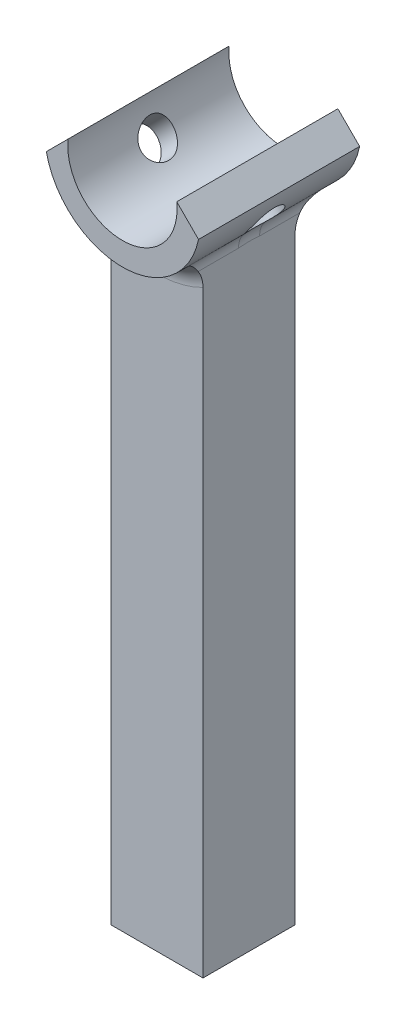
SolidWorks part; units mm, degrees
ref_plane "Front Plane" through (0, 0, 0) normal (0, 0, 1) x (1, 0, 0)
ref_plane "Top Plane" through (0, 0, 0) normal (0, 1, 0) x (1, 0, 0)
ref_plane "Right Plane" through (0, 0, 0) normal (1, 0, 0) x (0, 0, -1)
sketch "Sketch1" plane through (0, 0, 0) normal (0, 1, 0) x (1, 0, 0)
  line L1 (4, -15) -> (-4, -15)
  line L2 (4, -15) -> (4, -7)
  line L3 (4, -7) -> (-4, -7)
  line L4 (-4, -15) -> (-4, -7)
  point P4 (0, -7)
  dimension "D3" = 8
  dimension "D4" = 8
extrude "Boss-Extrude1" add sketch "Sketch1" against normal blind 55 contours L2 L3 L4 L1
sketch "Sketch2" plane through (0, 0, 0) normal (0, 0, 1) x (1, 0, 0)
  line L0 (-3.6183, 0) -> (3.4011, 0) construction
  line L1 (-8, 2) -> (8, 2) construction
  line L2 (-8, 2) -> (-4.4083, 5.5917)
  line L3 (8, 2) -> (3.6742, 6.3258)
  circle A0 centre (0, 4.75) radius 4.75
  circle A1 centre (0, 4.75) radius 6.75
  point P2 (-0.1086, 0)
  dimension "D1" = 0
  dimension "D3" = 2
  dimension "D4" = 45
  dimension "D5" = 45
  dimension "D6" = 8
  dimension "D7" = 8
  dimension "D2" = 2
extrude "Boss-Extrude2" add sketch "Sketch2" along normal blind 3 and the other way blind 11 from surface contours L2 A1 L3 A0 region at (-5.5591, 4.2274, 0) starting at face at (0, -27.5, 15)
ref_plane "Plane1" through (5, 5, 0) normal (0.7071, 0.7071, 0) x (0.7071, -0.7071, 0)
ref_plane "Plane2" through (-5.6066, -5.6066, 0) normal (-0.7071, -0.7071, 0) x (0.7071, -0.7071, 0)
sketch "Sketch4" plane through (-5.6066, -5.6066, 0) normal (-0.7071, -0.7071, 0) x (0.7071, -0.7071, 0)
  line L0 (-2.3425, 7) -> (-2.3425, 15) construction
  circle A0 centre (-4.3425, 11) radius 1.5
  point P4 (-2.3425, 11)
  dimension "D1" = 2
extrude "Cut-Extrude1" cut sketch "Sketch4" against normal through all
mirror "Mirror1" about plane through (0, 0, 0) normal (1, 0, 0) of "Cut-Extrude1"
fillet "Fillet1" radius 2 4 edges at (-4, -0.6871, 11) (0, -2, 7) (4, -0.6871, 11) (0, -2, 15)
